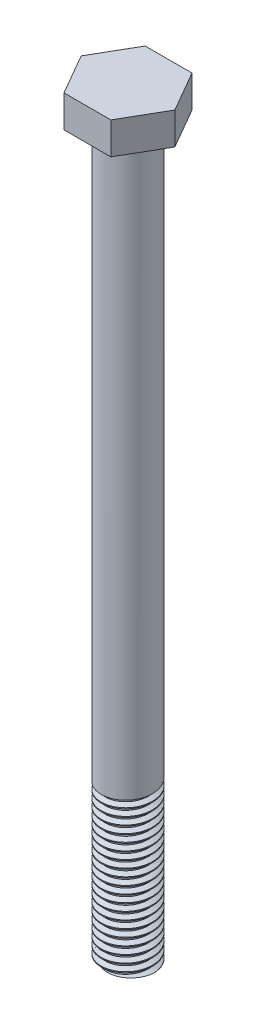
SolidWorks part; units mm, degrees
ref_plane "Front Plane" through (0, 0, 0) normal (0, 0, 1) x (1, 0, 0)
ref_plane "Top Plane" through (0, 0, 0) normal (0, 1, 0) x (1, 0, 0)
ref_plane "Right Plane" through (0, 0, 0) normal (1, 0, 0) x (0, 0, -1)
sketch "Sketch1" plane through (0, 0, 0) normal (0, 1, 0) x (1, 0, 0)
  circle A0 centre (0, 0) radius 6
  dimension "D1" = 12
extrude "Boss-Extrude1" add sketch "Sketch1" against normal blind 170
sketch "Sketch2" plane through (0, 0, 0) normal (0, 1, 0) x (1, 0, 0)
  line L1 (-5.4848, -9.5) -> (5.4848, -9.5)
  line L2 (5.4848, -9.5) -> (10.9697, 0)
  line L3 (10.9697, 0) -> (5.4848, 9.5)
  line L4 (5.4848, 9.5) -> (-5.4848, 9.5)
  line L5 (-5.4848, 9.5) -> (-10.9697, 0)
  line L6 (-10.9697, 0) -> (-5.4848, -9.5)
  circle A0 centre (0, 0) radius 9.5 construction
  dimension "D1" = 19
extrude "Boss-Extrude2" add sketch "Sketch2" along normal blind 7.5
thread "Thread1" pitch 1.75 method cut profile "Thread Profile1" start angle 0, offset 1.75, length 37.75, pitch 1.75, diameter 12
ref_plane "Plane1" through (6, -171.75, 0) normal (0, 0, 1) x (1, 0, 0)
sketch "Thread Profile1" plane through (6, -171.75, 0) normal (0, 0, 1) x (1, 0, 0)
  line L0 (0, 0) -> (0, 1.75) construction
  line L11 (0, 0) -> (0, 1.5312)
  line L12 (0, 1.5312) -> (-0.9472, 0.9844)
  line L13 (-0.9472, 0.9844) -> (-0.9472, 0.5469)
  line L15 (-0.9472, 0.5469) -> (0, 0)
  line L17 (-0.9472, 0.7656) -> (0, 0.7656) construction
  point P2 (0, 0)
  dimension "Pitch" = 1.75
  dimension "Profile_Angle" = 60
  dimension "Profile_Land" = 0.4375
  dimension "Profile_Height" = 0.9472
